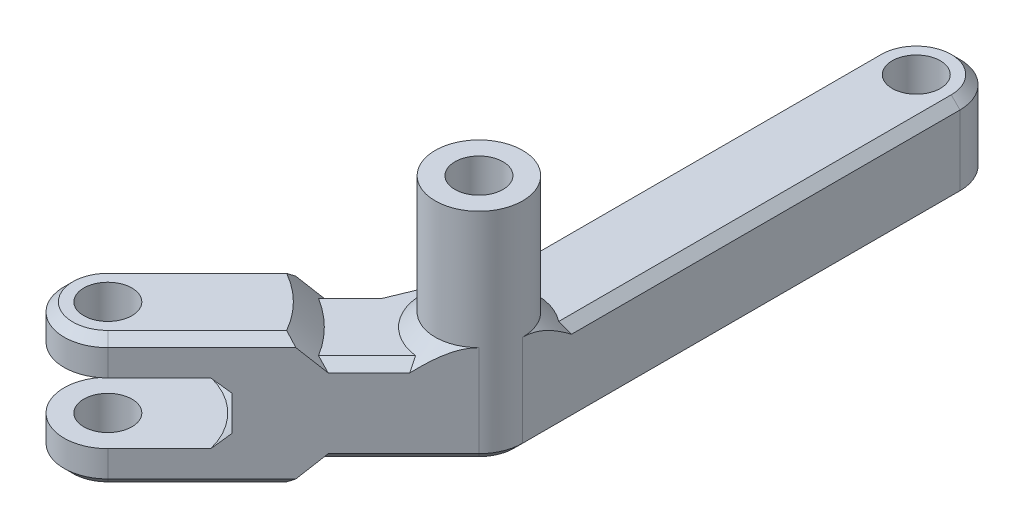
SolidWorks part; units mm, degrees
ref_plane "前视基准面" through (0, 0, 0) normal (0, 0, 1) x (1, 0, 0)
ref_plane "上视基准面" through (0, 0, 0) normal (0, 1, 0) x (1, 0, 0)
ref_plane "右视基准面" through (0, 0, 0) normal (1, 0, 0) x (0, 0, -1)
other "Configuration Table"
sketch "草图1" plane through (0, 0, 0) normal (0, 1, 0) x (1, 0, 0)
  line L0 (0, 0) -> (0, 50) construction
  line L1 (0, 0) -> (-21.2132, -21.2132) construction
  line L2 (-5, 2.0711) -> (-5, 50)
  line L3 (-17.6777, -24.7487) -> (3.5355, -3.5355)
  line L4 (-24.7487, -17.6777) -> (-5, 2.0711)
  line L5 (5, 0) -> (5, 50)
  arc A1 (-24.7487, -17.6777) -> (-17.6777, -24.7487) centre (-21.2132, -21.2132) ccw
  arc A2 (5, 50) -> (-5, 50) centre (0, 50) ccw
  arc A3 (3.5355, -3.5355) -> (5, 0) centre (0, 0) ccw
  dimension "D1" = 5
  dimension "D3" = 10
  dimension "D6" = 10
  dimension "D8" = 225
  dimension "D2" = 135
  dimension "D4" = 30
  dimension "D5" = 50
  dimension "D7" = 10
  dimension "D9" = 135
extrude "凸台-拉伸1" add sketch "草图1" along normal blind 10
sketch "草图3" plane through (0, 0, 0) normal (0, 1, 0) x (1, 0, 0)
  circle A0 centre (0, 0) radius 5
extrude "凸台-拉伸2" add sketch "草图3" along normal blind 25
sketch "草图4" plane through (0, 0, 0) normal (0, 1, 0) x (1, 0, 0)
  circle A0 centre (0, 0) radius 2.75
  dimension "D1" = 5.5
extrude "切除-拉伸1" cut sketch "草图4" along normal up to surface (25 mm away) from surface up to face at (0, 25, 5) starting at face at (-6.0107, 0, -8.204)
sketch "草图5" plane through (0, 0, 0) normal (0, 1, 0) x (1, 0, 0)
  circle A0 centre (-21.2132, -21.2132) radius 2.75
  dimension "D1" = 5.5
extrude "切除-拉伸2" cut sketch "草图5" against normal up to surface from surface up to face at (0, 0, 2.75) starting at face at (-7.3305, 10, -8.7507)
sketch "草图6" plane through (0, 0, 0) normal (0, 1, 0) x (1, 0, 0)
  circle A0 centre (-21.2132, -21.2132) radius 11.2
  dimension "D1" = 22.4
extrude "切除-拉伸3" cut sketch "草图6" along normal blind 7 from offset 1.5
sketch "草图7" plane through (0, 0, 0) normal (0, 1, 0) x (1, 0, 0)
  line L0 (-17.6777, -24.7487) -> (3.5355, -3.5355) construction
  line L1 (-5, 2.0711) -> (-24.7487, -17.6777) construction
  line L2 (-17.6777, -24.7487) -> (-7.6777, -14.7487)
  line L3 (-14.7487, -7.6777) -> (-24.7487, -17.6777)
  arc A0 (-7.6777, -14.7487) -> (-14.7487, -7.6777) centre (-21.2132, -21.2132) ccw
  arc A1 (-24.7487, -17.6777) -> (-17.6777, -24.7487) centre (-21.2132, -21.2132) ccw construction
  arc A2 (-24.7487, -17.6777) -> (-17.6777, -24.7487) centre (-21.2132, -21.2132) ccw
  dimension "D1" = 30
extrude "凸台-拉伸3" add sketch "草图7" along normal blind 2.5 from surface starting at face at (-21.2132, 10, 23.9632)
extrude "凸台-拉伸4" add sketch "草图7<2>" against normal blind 2.5
sketch "草图7<2>" plane through (0, 0, 0) normal (0, 1, 0) x (1, 0, 0) same geometry as "草图7"
chamfer "倒角1" distance 2.5 angle 45 2 edges at (-10.6066, 0, 10.6066) (-10.6066, 10, 10.6066)
sketch "草图8" plane through (0, 0, 0) normal (0, 1, 0) x (1, 0, 0)
  circle A0 centre (-21.2132, -21.2132) radius 2.75
  dimension "D1" = 5.5
extrude "切除-拉伸4" cut sketch "草图8" along normal up to surface (12.5 mm away) from surface up to face at (-16.9454, 12.5, 16.9454) starting at face at (-16.9454, -2.5, 16.9454)
sketch "草图9" plane through (0, 0, 0) normal (0, 1, 0) x (1, 0, 0)
  circle A0 centre (0, 50) radius 2.75
  dimension "D1" = 5.5
extrude "切除-拉伸5" cut sketch "草图9" against normal up to surface from surface up to face at (0, 0, 2.75) starting at face at (-3.3636, 10, -12.7176)
sketch "草图10" plane through (0, 0, 0) normal (0, 1, 0) x (1, 0, 0)
  line L0 (-5, 8.0711) -> (-9.2426, -2.1716)
  line L1 (-5, 50) -> (-5, 2.0711) construction
  line L2 (-5, 2.0711) -> (-12.8902, -5.8191) construction
  line L3 (-9.2426, -2.1716) -> (-5, 2.0711)
  line L4 (-5, 2.0711) -> (-5, 8.0711)
  dimension "D1" = 6
  dimension "D2" = 6
extrude "凸台-拉伸5" add sketch "草图10" against normal up to surface from surface up to face at (0, 0, -47.25) starting at face at (0, 10, -47.25)
chamfer "倒角2" distance 1.5 angle 45 3 edges at (-13.2936, 8.5, 13.2936) (-13.2936, 1.5, 13.2936) (-4.6194, 10, -1.9134)
chamfer "倒角3" distance 1 angle 45 19 edges at (-1.1418, 0, 8.2129) (-2.6102, 10, 9.6813) (5, 10, -27.0767) (0, 10, -55) (-5, 10, -29.0355) (-7.1213, 10, -2.9497) (-11.0664, 10, 3.9954) (-12.6777, 12.5, 19.7487) (-24.7487, 12.5, 24.7487) (-19.7487, 12.5, 12.6777) (-12.6777, -2.5, 19.7487) (-24.7487, -2.5, 24.7487) (-19.7487, -2.5, 12.6777) (4.6194, 0, 1.9134) (5, 0, -25) (0, 0, -55) (-11.0664, 0, 3.9954) (-7.1213, 0, -2.9497) (-5, 0, -29.0355)
